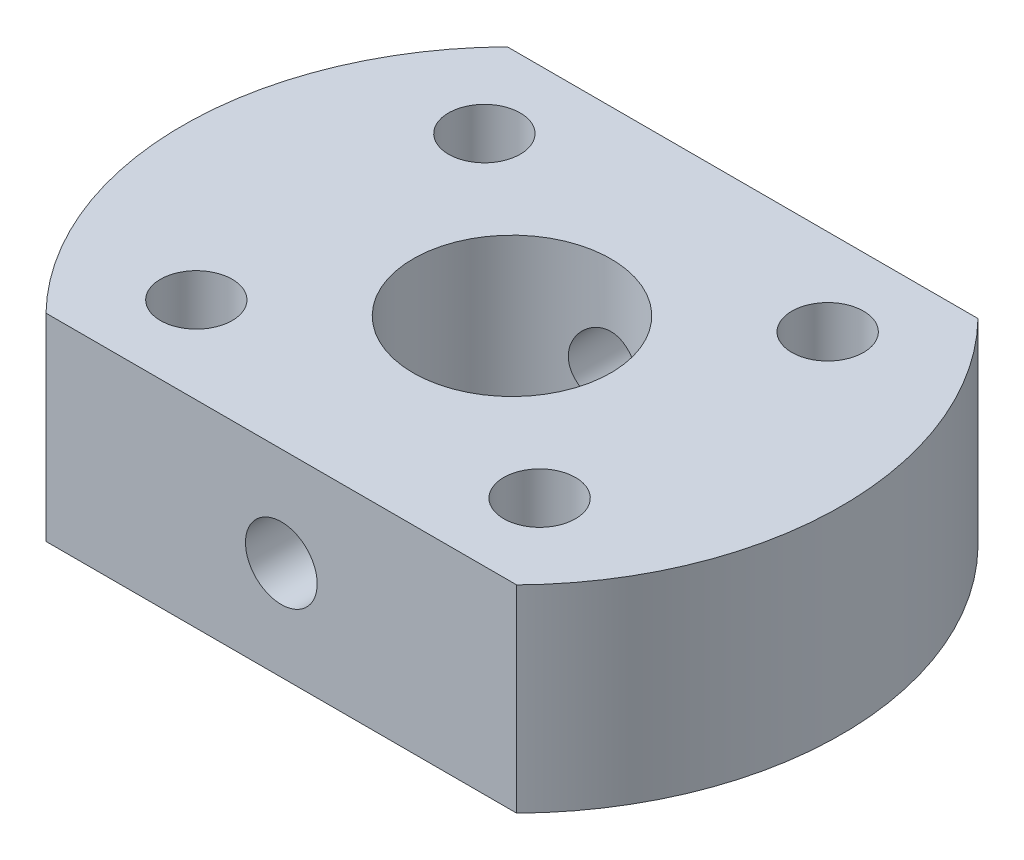
SolidWorks part; units mm, degrees
material "Alum Plate"
ref_plane "Front Plane" through (0, 0, 0) normal (0, 0, 1) x (1, 0, 0)
ref_plane "Top Plane" through (0, 0, 0) normal (0, 1, 0) x (1, 0, 0)
ref_plane "Right Plane" through (0, 0, 0) normal (1, 0, 0) x (0, 0, -1)
other "Bounding Box"
ref_plane "Default Plane" through (13.8565, 3.175, 6.7999) normal (0, -1, 0) x (-1, 0, 0)
sketch "Sketch1" plane through (0, 0, 0) normal (0, 1, 0) x (1, 0, 0)
  circle A0 centre (0, 0) radius 4.7625
  circle A1 centre (0, 0) radius 15.875
  dimension "D1" = 9.525
  dimension "D2" = 31.75
extrude "Boss-Extrude1" add sketch "Sketch1" along normal mid plane 9.525
sketch "Sketch2" plane through (0, 4.7625, 0) normal (0, 1, 0) x (1, 0, 0)
  line L0 (-11.337, 11.1125) -> (11.337, 11.1125)
  line L1 (-11.337, -11.1125) -> (11.337, -11.1125)
  circle A0 centre (0, 0) radius 15.875 construction
  arc A1 (-11.337, 11.1125) -> (11.337, 11.1125) centre (0, 0) cw
  arc A2 (-11.337, -11.1125) -> (11.337, -11.1125) centre (0, 0) ccw
  dimension "D1" = 22.225
extrude "Cut-Extrude1" cut sketch "Sketch2" against normal through all
sketch "Sketch3" plane through (0, 4.7625, 0) normal (0, 1, 0) x (1, 0, 0)
  line L0 (0, 0) -> (-8.2694, 6.9389) construction
  line L1 (0, 0) -> (0, 11.1125) construction
  line L2 (-11.337, 11.1125) -> (11.337, 11.1125) construction
  circle A0 centre (-8.2694, 6.9389) radius 1.7272
  point P7 (-5.6042, 5.8526)
  dimension "D1" = 3.4544
  dimension "D2" = 50
  dimension "D3" = 10.795
extrude "Cut-Extrude2" cut sketch "Sketch3" against normal blind 8.255
sketch "Sketch4" plane through (0, 0, 11.1125) normal (0, 0, 1) x (1, 0, 0)
  circle A0 centre (0, 0) radius 1.7272
  point P2 (0, 0)
  dimension "D1" = 3.4544
extrude "Cut-Extrude3" cut sketch "Sketch4" against normal through all
mirror "Mirror1" about plane through (0, 0, 0) normal (0, 0, 1) of "Cut-Extrude2"
mirror "Mirror2" about plane through (0, 0, 0) normal (1, 0, 0) of "Mirror1"
